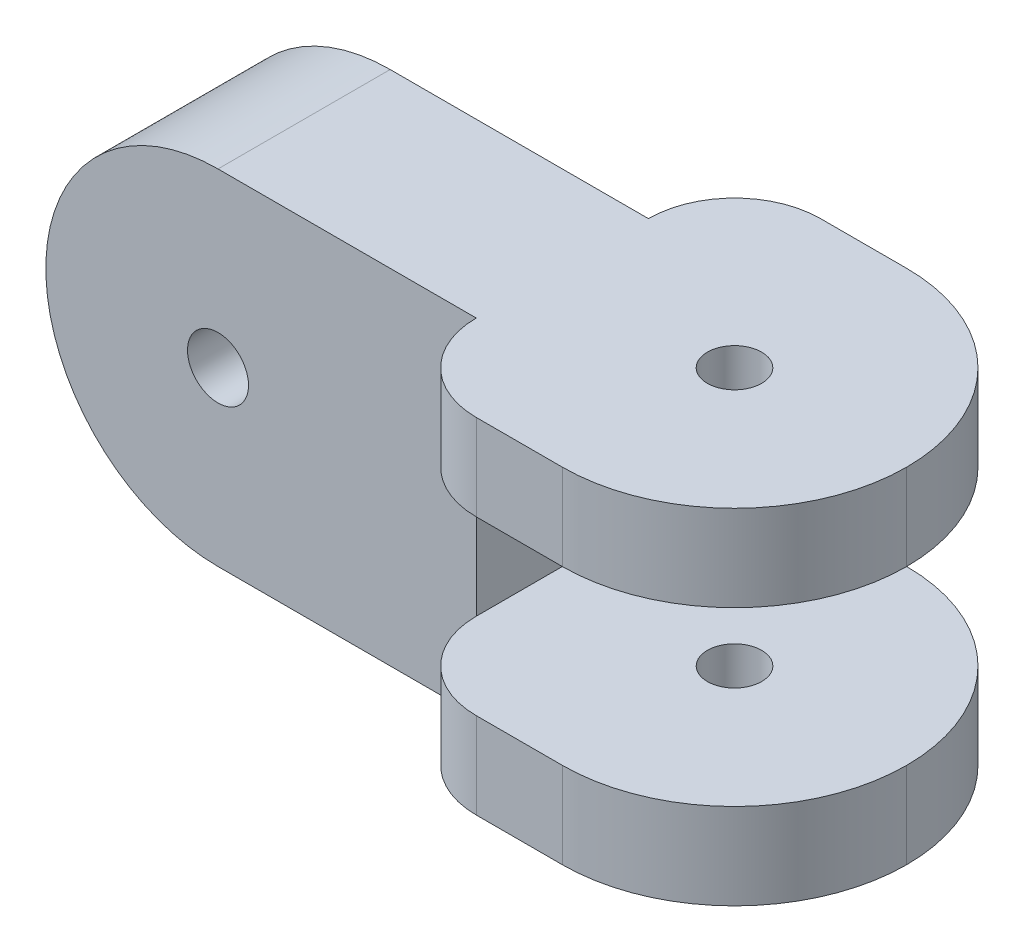
SolidWorks part; units mm, degrees
ref_plane "Front Plane" through (0, 0, 0) normal (0, 0, 1) x (1, 0, 0)
ref_plane "Top Plane" through (0, 0, 0) normal (0, 1, 0) x (1, 0, 0)
ref_plane "Right Plane" through (0, 0, 0) normal (1, 0, 0) x (0, 0, -1)
sketch "Sketch1" plane through (0, 0, 0) normal (0, 0, 1) x (1, 0, 0)
  line L1 (0, 12.7) -> (19.05, 12.7)
  line L3 (-10.1057, -12.7) -> (19.05, -12.7)
  line L4 (19.05, 12.7) -> (19.05, -12.7)
  arc A0 (0, 12.7) -> (0, -12.7) centre (0, 0) ccw
  circle A1 centre (0, 0) radius 2.25
  dimension "D1" = 25.4
  dimension "D2" = 4.5
  dimension "D3" = 25.4
  dimension "D4" = 19.05
extrude "Boss-Extrude1" add sketch "Sketch1" along normal blind 12.7 contours L1 A0 L3 L4 A1 region at (4.4963, 0, 0)
sketch "Sketch2" plane through (19.05, 0, 0) normal (1, 0, 0) x (0, 0, -1)
  line L1 (-19.05, 12.7) -> (6.35, 12.7)
  line L2 (-19.05, 12.7) -> (-19.05, -12.7)
  line L3 (-19.05, -12.7) -> (6.35, -12.7)
  line L4 (6.35, 12.7) -> (6.35, -12.7)
  line L5 (-12.7, 12.7) -> (0, 12.7) construction
  line L6 (-12.7, 12.7) -> (-12.7, -12.7) construction
  dimension "D1" = 25.4
  dimension "D2" = 25.4
  dimension "D3" = 6.35
extrude "Boss-Extrude2" add sketch "Sketch2" along normal blind 25.4 contours L1 L4 L3 L2
sketch "Sketch3" plane through (0, 0, 19.05) normal (0, 0, 1) x (1, 0, 0)
  line L0 (44.45, 12.7) -> (44.45, -12.7) construction
  line L1 (44.45, 6.35) -> (19.05, 6.35)
  line L2 (44.45, 6.35) -> (44.45, -6.35)
  line L3 (44.45, -6.35) -> (19.05, -6.35)
  line L4 (19.05, 6.35) -> (19.05, -6.35)
  line L5 (44.45, 12.7) -> (19.05, 12.7) construction
  line L6 (44.45, -12.7) -> (19.05, -12.7) construction
  dimension "D1" = 6.35
  dimension "D2" = 6.35
  dimension "D3" = 25.4
extrude "Cut-Extrude1" cut sketch "Sketch3" against normal blind 25.4
fillet "Fillet2" radius 6.35 4 edges at (19.05, 9.525, 19.05) (19.05, -9.525, 19.05) (19.05, -9.525, -6.35) (19.05, 9.525, -6.35)
fillet "Fillet3" radius 12.7 4 edges at (44.45, 9.525, 19.05) (44.45, -9.525, 19.05) (44.45, 9.525, -6.35) (44.45, -9.525, -6.35)
sketch "Sketch4" plane through (0, 12.7, 0) normal (0, 1, 0) x (1, 0, 0)
  circle A0 centre (31.75, -6.35) radius 2
  dimension "D1" = 4
extrude "Cut-Extrude2" cut sketch "Sketch4" against normal blind 25.4
